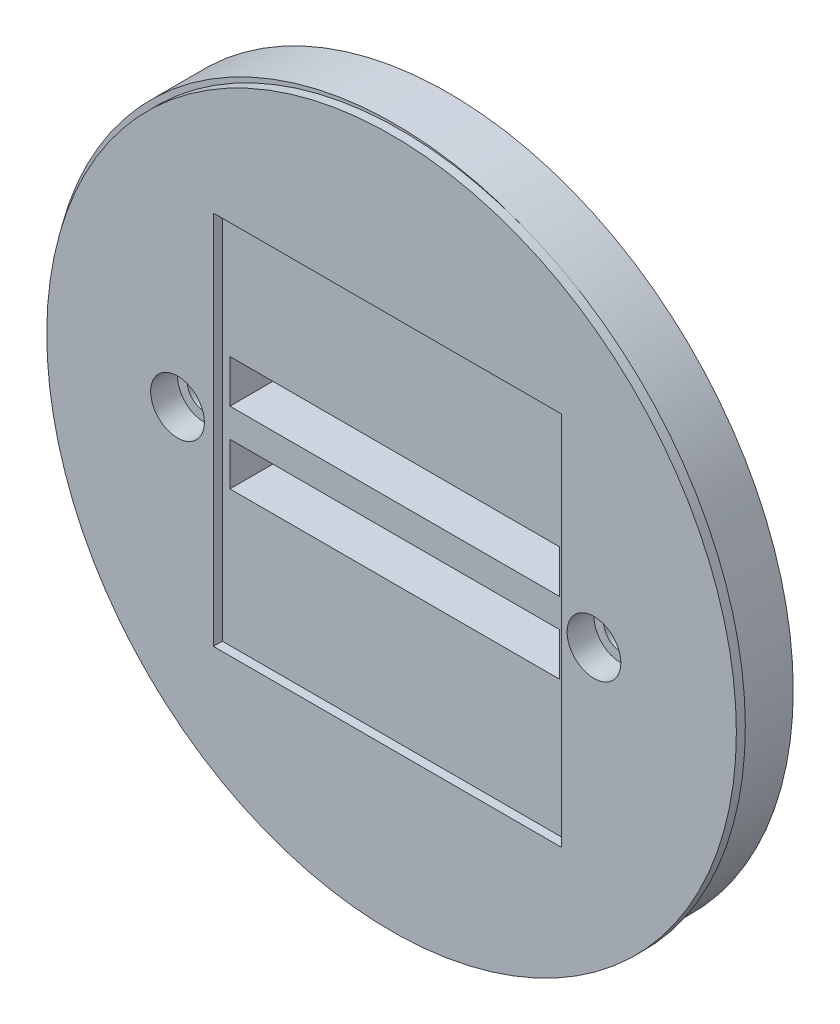
SolidWorks part; units mm, degrees
material "ABS"
ref_plane "Front Plane" through (0, 0, 0) normal (0, 0, 1) x (1, 0, 0)
ref_plane "Top Plane" through (0, 0, 0) normal (0, 1, 0) x (1, 0, 0)
ref_plane "Right Plane" through (0, 0, 0) normal (1, 0, 0) x (0, 0, -1)
sketch "Sketch1" plane through (0, 0, 0) normal (0, 0, 1) x (1, 0, 0)
  line L0 (18.4, 6.8) -> (18.4, 2)
  line L2 (-18.4, 6.8) -> (18.4, 6.8)
  line L3 (18.4, -1.2) -> (-18.4, -1.2)
  line L4 (-18.4, 2) -> (-18.4, 6.8)
  line L5 (-18.4, -1.2) -> (-18.4, -6)
  line L6 (-18.4, -6) -> (18.4, -6)
  line L7 (18.4, -6) -> (18.4, -1.2)
  line L8 (18.4, 2) -> (-18.4, 2)
  circle A0 centre (-23.25, 0) radius 1.925
  circle A1 centre (0, 0) radius 34.7 construction
  circle A2 centre (23.25, 0) radius 1.925
  circle A6 centre (0, 0) radius 38.5
  dimension "D2" = 69.4
  dimension "D5" = 77
  dimension "D10" = 3.85
  dimension "D8" = 3.85
  dimension "D3" = 18.4
  dimension "D4" = 23.25
  dimension "D6" = 18.4
  dimension "D7" = 23.25
  dimension "D9" = 4.8
extrude "Main Flange Coupling" add sketch "Sketch1" against normal blind 6
sketch "Sketch2" plane through (0, 0, 0) normal (0, 0, 1) x (1, 0, 0)
  line L0 (-19.25, 20.75) -> (19.65, 20.75)
  line L1 (-19.25, 20.75) -> (-19.25, -21.15)
  line L2 (-19.25, -21.15) -> (19.65, -21.15)
  line L3 (19.65, 20.75) -> (19.65, -21.15)
  line L4 (-19.25, 20.75) -> (19.65, -21.15) construction
  line L5 (-19.25, -21.15) -> (19.65, 20.75) construction
  circle A0 centre (0.65, -0.25) radius 38.5
  circle A1 centre (-23.25, 0) radius 1.7
  circle A2 centre (23.25, 0) radius 1.7
  dimension "D3" = 77
  dimension "D4" = 3.4
  dimension "D5" = 3.4
  dimension "D1" = 38.9
  dimension "D2" = 41.9
  dimension "D6" = 21
  dimension "D7" = 19
extrude "Boss-Extrude1" add sketch "Sketch2" along normal blind 1
sketch "Sketch3" plane through (0, 0, 1) normal (0, 0, 1) x (1, 0, 0)
  circle A0 centre (-23.25, 0) radius 3
  circle A1 centre (23.25, 0) radius 3
  dimension "D1" = 6
  dimension "D2" = 6
extrude "Cut-Extrude1" cut sketch "Sketch3" against normal blind 3
equation "\"D4@Sketch2\"= 3 + \"tol1@parametersSketch@prostheticParameters.SLDPRT\""
equation "\"D5@Sketch2\"= 3 + \"tol1@parametersSketch@prostheticParameters.SLDPRT\""
equation "\"D1@Sketch2\"= 38.5 + \"tol2@parametersSketch@prostheticParameters.SLDPRT\""
equation "\"D2@Sketch2\"= 41.5 + \"tol2@parametersSketch@prostheticParameters.SLDPRT\""
equation "\"D8@Sketch1\"= 3.45 + \"tol1@parametersSketch@prostheticParameters.SLDPRT\""
equation "\"D10@Sketch1\"= 3.45 + \"tol1@parametersSketch@prostheticParameters.SLDPRT\""
equation "\"D3@Sketch1\"= 18 + \"tol2@parametersSketch@prostheticParameters.SLDPRT\""
equation "\"D6@Sketch1\" = 18 + \"tol2@parametersSketch@prostheticParameters.SLDPRT\""
equation "\"D9@Sketch1\"= 4 + \"tol2@parametersSketch@prostheticParameters.SLDPRT\" * 2"
